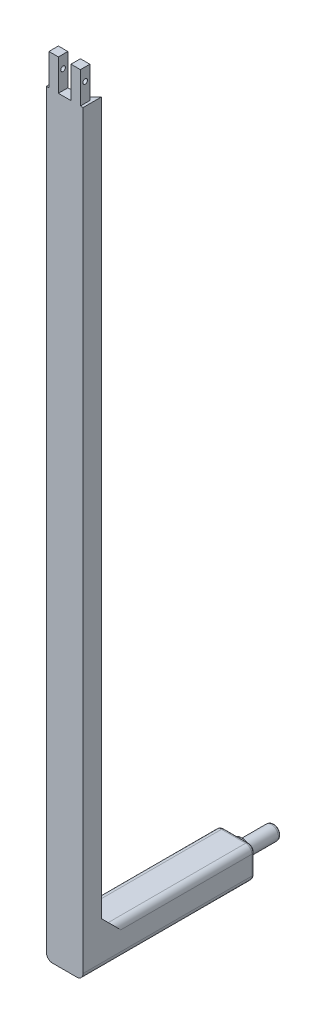
SolidWorks part; units mm, degrees
ref_plane "Front Plane" through (0, 0, 0) normal (0, 0, 1) x (1, 0, 0)
ref_plane "Top Plane" through (0, 0, 0) normal (0, 1, 0) x (1, 0, 0)
ref_plane "Right Plane" through (0, 0, 0) normal (1, 0, 0) x (0, 0, -1)
sketch "Sketch2" plane through (0, 0, 0) normal (0, 0, 1) x (1, 0, 0)
  line L1 (0, 0) -> (-6, 0)
  line L2 (0, 0) -> (0, -240)
  line L3 (0, -240) -> (-6, -240)
  line L4 (-6, 0) -> (-6, -240)
  dimension "D1" = 6
  dimension "D2" = 240
extrude "Boss-Extrude1" add sketch "Sketch2" along normal blind 3
sketch "Sketch4" plane through (0, -240, 0) normal (0, -1, 0) x (-1, 0, 0)
  line L0 (0, 0) -> (-2.8284, 2.8284)
  line L1 (-2.8284, 2.8284) -> (-2.8284, -3)
  line L2 (-2.8284, -3) -> (0, -3)
  line L3 (0, -3) -> (0, 0)
  line L4 (3, 0) -> (3, -3.7119) construction
  line L5 (6, 0) -> (0, 0) construction
  line L6 (8.8284, -3) -> (6, -3)
  line L7 (8.8284, 2.8284) -> (8.8284, -3)
  line L8 (6, 0) -> (8.8284, 2.8284)
  line L9 (6, -3) -> (6, 0)
  dimension "D1" = 135
  dimension "D2" = 4
extrude "Boss-Extrude2" add sketch "Sketch4" against normal up to vertex (240 mm away) up to point (0, 0, 0)
sketch "Sketch5" plane through (0, 0, 0) normal (0, 1, 0) x (1, 0, 0)
  line L0 (2.8284, -3) -> (-8.8284, -3) construction
  line L1 (-8, -3) -> (-5, -3)
  line L2 (-8, -3) -> (-8, 0)
  line L3 (-8, 0) -> (-5, 0)
  line L4 (-5, -3) -> (-5, 0)
  line L5 (-3, 0) -> (-3, -4.0355) construction
  line L6 (0, 0) -> (-6, 0) construction
  line L7 (2, 0) -> (-1, 0)
  line L8 (-1, -3) -> (-1, 0)
  line L9 (2, -3) -> (-1, -3)
  line L10 (2, -3) -> (2, 0)
  dimension "D1" = 3
  dimension "D2" = 2
  dimension "D3" = 0
extrude "Boss-Extrude3" add sketch "Sketch5" along normal blind 10
sketch "Sketch6" plane through (2, 0, 0) normal (1, 0, 0) x (0, 0, -1)
  line L0 (-3, 10) -> (-3, 0) construction
  line L1 (-3, 10) -> (0, 10) construction
  circle A0 centre (-1.5, 6) radius 0.75
  dimension "D1" = 1.5
  dimension "D2" = 1.5
  dimension "D3" = 4
extrude "Cut-Extrude1" cut sketch "Sketch6" against normal blind 40
sketch "Sketch7" plane through (0, 0, 0) normal (0, 0, -1) x (-1, 0, 0)
  line L0 (-2.8284, 0) -> (-2.8284, -240) construction
  line L1 (8.8284, -240) -> (-2.8284, -240)
  line L2 (8.8284, -240) -> (8.8284, -230)
  line L3 (8.8284, -230) -> (-2.8284, -230)
  line L4 (-2.8284, -240) -> (-2.8284, -230)
  dimension "D1" = 10
extrude "Boss-Extrude4" add sketch "Sketch7" along normal blind 51.58
sketch "Sketch8" plane through (0, 0, -51.58) normal (0, 0, -1) x (-1, 0, 0)
  line L0 (-2.8284, -240) -> (8.8284, -240) construction
  line L1 (-2.8284, -230) -> (-2.8284, -240) construction
  circle A0 centre (3, -235) radius 2.25
  point P4 (3, -240)
  point P7 (-2.8284, -235)
  dimension "D1" = 0
  dimension "D2" = 0
  dimension "D3" = 4.5
extrude "Boss-Extrude5" add sketch "Sketch8" along normal blind 12
sketch "Sketch9" plane through (-8.8284, 0, 0) normal (-1, 0, 0) x (0, 0, 1)
  line L0 (-7, -230) -> (0, -230)
  line L1 (-51.58, -230) -> (-2.8284, -230) construction
  line L2 (0, -230) -> (0, -223)
  line L3 (0, -223) -> (-7, -230)
  dimension "D1" = 7
  dimension "D2" = 7
extrude "Boss-Extrude6" add sketch "Sketch9" against normal up to vertex (11.6569 mm away) up to point (2.8284, -230, -2.8284)
sketch "Sketch10" plane through (0, 0, -51.58) normal (0, 0, -1) x (-1, 0, 0)
  circle A0 centre (3, -235) radius 3.5
  dimension "D1" = 7
extrude "Boss-Extrude7" add sketch "Sketch10" along normal blind 2
fillet "Fillet1" radius 2 4 edges at (2.8284, -240, -24.29) (-8.8284, -240, -24.29) (2.8284, -230, -29.29) (-8.8284, -230, -29.29)
fillet "Fillet2" radius 1 9 edges at (-8.2426, -239.4142, -51.58) (2.2426, -239.4142, -51.58) (2.2426, -230.5858, -51.58) (-8.2426, -230.5858, -51.58) (-6.5, -235, -53.58) (-3, -240, -51.58) (2.8284, -235, -51.58) (-3, -230, -51.58) (-8.8284, -235, -51.58)
fillet "Fillet3" radius 1 1 edges at (-5.25, -235, -63.58)
